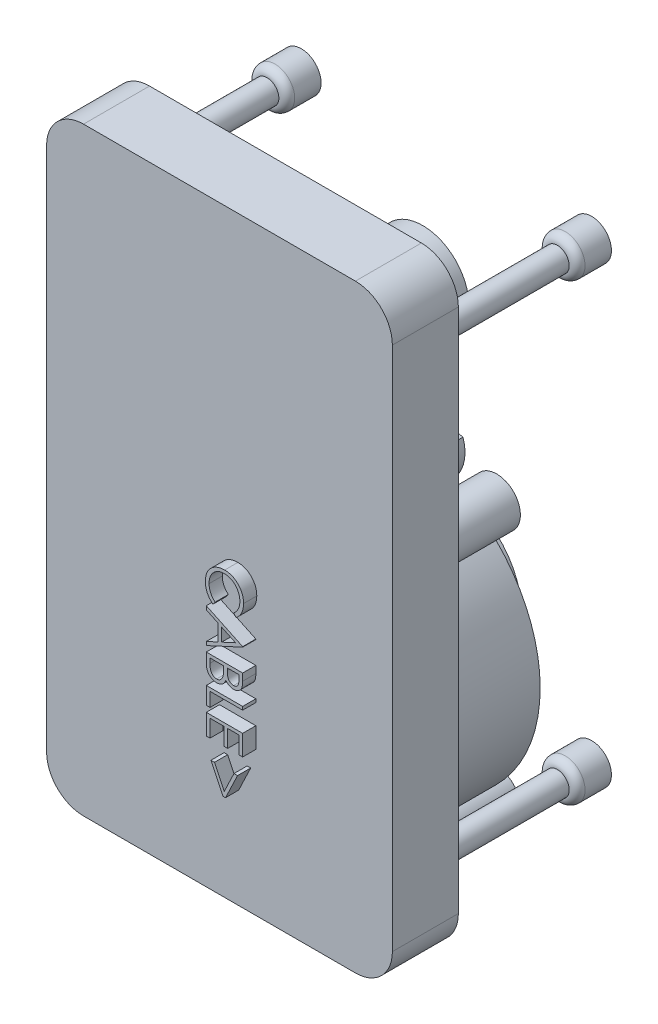
SolidWorks part; units mm, degrees
ref_plane "Front Plane" through (0, 0, 0) normal (0, 0, 1) x (1, 0, 0)
ref_plane "Top Plane" through (0, 0, 0) normal (0, 1, 0) x (1, 0, 0)
ref_plane "Right Plane" through (0, 0, 0) normal (1, 0, 0) x (0, 0, -1)
sketch "Sketch1" plane through (0, 0, 0) normal (0, 0, 1) x (1, 0, 0)
  line L0 (-13.081, 28.829) -> (13.081, 28.829)
  line L1 (-16.637, 25.273) -> (-16.637, -25.273)
  line L2 (-13.081, -28.829) -> (13.081, -28.829)
  line L3 (16.637, 25.273) -> (16.637, -25.273)
  line L4 (-16.637, 28.829) -> (16.637, -28.829) construction
  line L5 (-16.637, -28.829) -> (16.637, 28.829) construction
  line L6 (0, 36.9388) -> (0, -36.9388) construction
  line L7 (-21.0275, 0) -> (21.0275, 0) construction
  arc A0 (16.637, -25.273) -> (13.081, -28.829) centre (13.081, -25.273) cw
  arc A1 (-13.081, -28.829) -> (-16.637, -25.273) centre (-13.081, -25.273) cw
  arc A2 (16.637, 25.273) -> (13.081, 28.829) centre (13.081, 25.273) ccw
  arc A3 (-13.081, 28.829) -> (-16.637, 25.273) centre (-13.081, 25.273) ccw
  circle A4 centre (0, -12.7) radius 7.239
  circle A5 centre (0, 12.7) radius 4.445
  circle A6 centre (0, 14.605) radius 6.35
  circle A7 centre (0, -12.7) radius 14.351
  arc A8 (-3.6204, 1.1868) -> (3.6204, 1.1868) centre (0, 0) ccw
  circle A9 centre (13.97, 21.844) radius 1.016
  circle A10 centre (-13.97, 21.844) radius 1.016
  circle A11 centre (13.97, -21.844) radius 1.016
  circle A12 centre (-13.97, -21.844) radius 1.016
  arc A13 (6.6635, 0.0102) -> (10.0641, -2.4694) centre (8.89, -0.508) cw
  arc A14 (-10.0641, -2.4694) -> (-6.6635, 0.0102) centre (-8.89, -0.508) cw
  arc A15 (-10.0641, -22.9306) -> (-6.6635, -25.4102) centre (-8.89, -24.892) ccw
  arc A16 (6.6635, -25.4102) -> (10.0641, -22.9306) centre (8.89, -24.892) ccw
  point P0 (0, 0)
  dimension "D3" = 3.556
  dimension "D4" = 14.478
  dimension "D5" = 8.89
  dimension "D6" = 12.7
  dimension "D8" = 7.62
  dimension "D10" = 2.032
  dimension "D12" = 28.702
  dimension "D13" = 2.286
  dimension "D1" = 33.274
  dimension "D2" = 57.658
  dimension "D7" = 12.7
  dimension "D9" = 21.844
  dimension "D11" = 13.97
  dimension "D14" = 8.89
  dimension "D15" = 0.508
  dimension "D16" = 0.508
  dimension "D17" = 8.89
  dimension "D18" = 24.892
  dimension "D19" = 24.892
  dimension "D20" = 8.89
  dimension "D21" = 8.89
extrude "Boss-Extrude1" add sketch "Sketch1" against normal blind 10.16 contours A8 A7 A4 | A14 A7 | A7 A8 | A13 A7 | A7 A16 | A7 A15 | A4 region at (0, -12.7, 0) region at (12.8646, -18.0906, 0) region at (9.2197, -0.0559, 0) region at (9.2197, -25.3441, 0) region at (0, -0.8411, 0) region at (-9.2197, -25.3441, 0) region at (-9.2197, -0.0559, 0)
sketch "Sketch2" plane through (0, 0, 0) normal (0, 0, 1) x (1, 0, 0)
  line L0 (-13.081, 28.829) -> (13.081, 28.829)
  line L1 (-16.637, 25.273) -> (-16.637, -25.273)
  line L2 (-13.081, -28.829) -> (13.081, -28.829)
  line L3 (16.637, 25.273) -> (16.637, -25.273)
  line L4 (-16.637, 28.829) -> (16.637, -28.829) construction
  line L5 (-16.637, -28.829) -> (16.637, 28.829) construction
  line L6 (0, 38.9705) -> (0, -34.9071) construction
  line L7 (-9.8575, 0) -> (32.1974, 0) construction
  arc A0 (16.637, -25.273) -> (13.081, -28.829) centre (13.081, -25.273) cw
  arc A1 (-13.081, -28.829) -> (-16.637, -25.273) centre (-13.081, -25.273) cw
  arc A2 (16.637, 25.273) -> (13.081, 28.829) centre (13.081, 25.273) ccw
  arc A3 (-13.081, 28.829) -> (-16.637, 25.273) centre (-13.081, 25.273) ccw
  circle A4 centre (0, -12.7) radius 7.239
  circle A5 centre (0, 12.7) radius 4.445
  circle A6 centre (0, 14.605) radius 6.35
  circle A7 centre (0, -12.7) radius 14.351
  arc A8 (-3.6204, 1.1868) -> (3.6204, 1.1868) centre (0, 0) ccw
  circle A9 centre (13.97, 21.844) radius 1.016
  circle A10 centre (-13.97, 21.844) radius 1.016
  circle A11 centre (13.97, -21.844) radius 1.016
  circle A12 centre (-13.97, -21.844) radius 1.016
  arc A13 (6.6635, 0.0102) -> (10.0641, -2.4694) centre (8.89, -0.508) cw
  arc A14 (-10.0641, -2.4694) -> (-6.6635, 0.0102) centre (-8.89, -0.508) cw
  arc A15 (-10.0641, -22.9306) -> (-6.6635, -25.4102) centre (-8.89, -24.892) ccw
  arc A16 (6.6635, -25.4102) -> (10.0641, -22.9306) centre (8.89, -24.892) ccw
  point P0 (0, 0)
  dimension "D3" = 3.556
  dimension "D4" = 14.478
  dimension "D5" = 8.89
  dimension "D6" = 12.7
  dimension "D8" = 7.62
  dimension "D10" = 2.032
  dimension "D12" = 28.702
  dimension "D13" = 2.286
  dimension "D1" = 33.274
  dimension "D2" = 57.658
  dimension "D7" = 12.7
  dimension "D9" = 21.844
  dimension "D11" = 13.97
  dimension "D14" = 8.89
  dimension "D15" = 0.508
  dimension "D16" = 0.508
  dimension "D17" = 8.89
  dimension "D18" = 24.892
  dimension "D19" = 24.892
  dimension "D20" = 8.89
  dimension "D21" = 8.89
extrude "Boss-Extrude2" add sketch "Sketch2" against normal blind 1.778 separate body contours A5 | A5 A6 region at (0, 12.7, 0) region at (-4.3631, 18.9681, 0)
sketch "Sketch3" plane through (0, 0, -10.16) normal (0, 0, -1) x (-1, 0, 0)
  circle A0 centre (-8.89, -0.508) radius 2.286
  circle A1 centre (8.89, -24.892) radius 2.286
  circle A2 centre (-8.89, -24.892) radius 2.286
  circle A3 centre (8.89, -0.508) radius 2.286
extrude "Boss-Extrude3" add sketch "Sketch3" along normal blind 1.27
sketch "Sketch4" plane through (0, 0, -10.16) normal (0, 0, -1) x (-1, 0, 0)
  line L0 (-13.081, 28.829) -> (13.081, 28.829)
  line L1 (-16.637, 25.273) -> (-16.637, -25.273)
  line L2 (-13.081, -28.829) -> (13.081, -28.829)
  line L3 (16.637, 25.273) -> (16.637, -25.273)
  line L4 (-16.637, 28.829) -> (16.637, -28.829) construction
  line L5 (-16.637, -28.829) -> (16.637, 28.829) construction
  line L6 (0, 23.9866) -> (0, -49.891) construction
  line L7 (7.1619, 0) -> (49.2169, 0) construction
  arc A0 (16.637, -25.273) -> (13.081, -28.829) centre (13.081, -25.273) cw
  arc A1 (-13.081, -28.829) -> (-16.637, -25.273) centre (-13.081, -25.273) cw
  arc A2 (16.637, 25.273) -> (13.081, 28.829) centre (13.081, 25.273) ccw
  arc A3 (-13.081, 28.829) -> (-16.637, 25.273) centre (-13.081, 25.273) ccw
  circle A4 centre (0, -12.7) radius 7.239
  circle A5 centre (0, 12.7) radius 4.445
  circle A6 centre (0, 14.605) radius 6.35
  circle A7 centre (0, -12.7) radius 14.351
  arc A8 (-3.6204, 1.1868) -> (3.6204, 1.1868) centre (0, 0) ccw
  circle A9 centre (13.97, 21.844) radius 1.016
  circle A10 centre (-13.97, 21.844) radius 1.016
  circle A11 centre (13.97, -21.844) radius 1.016
  circle A12 centre (-13.97, -21.844) radius 1.016
  arc A13 (6.6635, 0.0102) -> (10.0641, -2.4694) centre (8.89, -0.508) cw
  arc A14 (-10.0641, -2.4694) -> (-6.6635, 0.0102) centre (-8.89, -0.508) cw
  arc A15 (-10.0641, -22.9306) -> (-6.6635, -25.4102) centre (-8.89, -24.892) ccw
  arc A16 (6.6635, -25.4102) -> (10.0641, -22.9306) centre (8.89, -24.892) ccw
  point P0 (0, 0)
  dimension "D3" = 3.556
  dimension "D4" = 14.478
  dimension "D5" = 8.89
  dimension "D6" = 12.7
  dimension "D8" = 7.62
  dimension "D10" = 2.032
  dimension "D12" = 28.702
  dimension "D13" = 2.286
  dimension "D1" = 33.274
  dimension "D2" = 57.658
  dimension "D7" = 12.7
  dimension "D9" = 21.844
  dimension "D11" = 13.97
  dimension "D14" = 8.89
  dimension "D15" = 0.508
  dimension "D16" = 0.508
  dimension "D17" = 8.89
  dimension "D18" = 24.892
  dimension "D19" = 24.892
  dimension "D20" = 8.89
  dimension "D21" = 8.89
extrude "Boss-Extrude4" add sketch "Sketch4" along normal blind 3.302 contours A7 A8 region at (0, -0.8411, -10.16)
sketch "Sketch5" plane through (0, 0, -1.778) normal (0, 0, -1) x (-1, 0, 0)
  line L0 (-13.081, 28.829) -> (13.081, 28.829)
  line L1 (-16.637, 25.273) -> (-16.637, -25.273)
  line L2 (-13.081, -28.829) -> (13.081, -28.829)
  line L3 (16.637, 25.273) -> (16.637, -25.273)
  line L4 (-16.637, 28.829) -> (16.637, -28.829) construction
  line L5 (-16.637, -28.829) -> (16.637, 28.829) construction
  line L6 (0, 36.0331) -> (0, -37.8445) construction
  line L7 (26.8703, 0) -> (68.9252, 0) construction
  arc A0 (16.637, -25.273) -> (13.081, -28.829) centre (13.081, -25.273) cw
  arc A1 (-13.081, -28.829) -> (-16.637, -25.273) centre (-13.081, -25.273) cw
  arc A2 (16.637, 25.273) -> (13.081, 28.829) centre (13.081, 25.273) ccw
  arc A3 (-13.081, 28.829) -> (-16.637, 25.273) centre (-13.081, 25.273) ccw
  circle A4 centre (0, -12.7) radius 7.239
  circle A5 centre (0, 12.7) radius 4.445
  circle A6 centre (0, 14.605) radius 6.35
  circle A7 centre (0, -12.7) radius 14.351
  arc A8 (-3.6204, 1.1868) -> (3.6204, 1.1868) centre (0, 0) ccw
  circle A9 centre (13.97, 21.844) radius 1.016
  circle A10 centre (-13.97, 21.844) radius 1.016
  circle A11 centre (13.97, -21.844) radius 1.016
  circle A12 centre (-13.97, -21.844) radius 1.016
  arc A13 (6.6635, 0.0102) -> (10.0641, -2.4694) centre (8.89, -0.508) cw
  arc A14 (-10.0641, -2.4694) -> (-6.6635, 0.0102) centre (-8.89, -0.508) cw
  arc A15 (-10.0641, -22.9306) -> (-6.6635, -25.4102) centre (-8.89, -24.892) ccw
  arc A16 (6.6635, -25.4102) -> (10.0641, -22.9306) centre (8.89, -24.892) ccw
  point P0 (0, 0)
  dimension "D3" = 3.556
  dimension "D4" = 14.478
  dimension "D5" = 8.89
  dimension "D6" = 12.7
  dimension "D8" = 7.62
  dimension "D10" = 2.032
  dimension "D12" = 28.702
  dimension "D13" = 2.286
  dimension "D1" = 33.274
  dimension "D2" = 57.658
  dimension "D7" = 12.7
  dimension "D9" = 21.844
  dimension "D11" = 13.97
  dimension "D14" = 8.89
  dimension "D15" = 0.508
  dimension "D16" = 0.508
  dimension "D17" = 8.89
  dimension "D18" = 24.892
  dimension "D19" = 24.892
  dimension "D20" = 8.89
  dimension "D21" = 8.89
extrude "Boss-Extrude5" add sketch "Sketch5" along normal blind 11.43 contours A5 region at (0, 12.7, -1.778)
sketch "Sketch6" plane through (0, 0, 0) normal (0, 0, 1) x (1, 0, 0)
  line L0 (-13.081, 28.829) -> (13.081, 28.829)
  line L1 (-16.637, 25.273) -> (-16.637, -25.273)
  line L2 (-13.081, -28.829) -> (13.081, -28.829)
  line L3 (16.637, 25.273) -> (16.637, -25.273)
  line L4 (-16.637, 28.829) -> (16.637, -28.829) construction
  line L5 (-16.637, -28.829) -> (16.637, 28.829) construction
  line L6 (0, 36.0885) -> (0, -37.789) construction
  line L7 (-47.9194, 0) -> (-5.8644, 0) construction
  arc A0 (16.637, -25.273) -> (13.081, -28.829) centre (13.081, -25.273) cw
  arc A1 (-13.081, -28.829) -> (-16.637, -25.273) centre (-13.081, -25.273) cw
  arc A2 (16.637, 25.273) -> (13.081, 28.829) centre (13.081, 25.273) ccw
  arc A3 (-13.081, 28.829) -> (-16.637, 25.273) centre (-13.081, 25.273) ccw
  circle A4 centre (0, -12.7) radius 7.239
  circle A5 centre (0, 12.7) radius 4.445
  circle A6 centre (0, 14.605) radius 6.35
  circle A7 centre (0, -12.7) radius 14.351
  arc A8 (-3.6204, 1.1868) -> (3.6204, 1.1868) centre (0, 0) ccw
  circle A9 centre (13.97, 21.844) radius 1.143
  circle A10 centre (-13.97, 21.844) radius 1.143
  circle A11 centre (13.97, -21.844) radius 1.143
  circle A12 centre (-13.97, -21.844) radius 1.143
  arc A13 (6.6635, 0.0102) -> (10.0641, -2.4694) centre (8.89, -0.508) cw
  arc A14 (-10.0641, -2.4694) -> (-6.6635, 0.0102) centre (-8.89, -0.508) cw
  arc A15 (-10.0641, -22.9306) -> (-6.6635, -25.4102) centre (-8.89, -24.892) ccw
  arc A16 (6.6635, -25.4102) -> (10.0641, -22.9306) centre (8.89, -24.892) ccw
  point P0 (0, 0)
  dimension "D3" = 3.556
  dimension "D4" = 14.478
  dimension "D5" = 8.89
  dimension "D6" = 12.7
  dimension "D8" = 7.62
  dimension "D10" = 2.286
  dimension "D12" = 28.702
  dimension "D13" = 2.286
  dimension "D1" = 33.274
  dimension "D2" = 57.658
  dimension "D7" = 12.7
  dimension "D9" = 21.844
  dimension "D11" = 13.97
  dimension "D14" = 8.89
  dimension "D15" = 0.508
  dimension "D16" = 0.508
  dimension "D17" = 8.89
  dimension "D18" = 24.892
  dimension "D19" = 24.892
  dimension "D20" = 8.89
  dimension "D21" = 8.89
extrude "Boss-Extrude6" add sketch "Sketch6" against normal blind 15.494 separate body contours A10 | A9 | A12 | A11 region at (13.97, 21.844, 0) region at (-13.97, 21.844, 0) region at (13.97, -21.844, 0) region at (-13.97, -21.844, 0)
sketch "Sketch7" plane through (0, 0, -10.16) normal (0, 0, -1) x (-1, 0, 0)
  line L0 (-13.081, 28.829) -> (13.081, 28.829)
  line L1 (-16.637, 25.273) -> (-16.637, -25.273)
  line L2 (-13.081, -28.829) -> (13.081, -28.829)
  line L3 (16.637, 25.273) -> (16.637, -25.273)
  line L4 (-16.637, 28.829) -> (16.637, -28.829) construction
  line L5 (-16.637, -28.829) -> (16.637, 28.829) construction
  line L6 (0, 26.9541) -> (0, -46.9235) construction
  line L7 (8.0915, 0) -> (50.1464, 0) construction
  arc A0 (16.637, -25.273) -> (13.081, -28.829) centre (13.081, -25.273) cw
  arc A1 (-13.081, -28.829) -> (-16.637, -25.273) centre (-13.081, -25.273) cw
  arc A2 (16.637, 25.273) -> (13.081, 28.829) centre (13.081, 25.273) ccw
  arc A3 (-13.081, 28.829) -> (-16.637, 25.273) centre (-13.081, 25.273) ccw
  circle A4 centre (0, -12.7) radius 7.239
  circle A5 centre (0, 12.7) radius 4.445
  circle A6 centre (0, 14.605) radius 6.35
  circle A7 centre (0, -12.7) radius 14.351
  arc A8 (-3.6204, 1.1868) -> (3.6204, 1.1868) centre (0, 0) ccw
  circle A9 centre (13.97, 21.844) radius 1.016
  circle A10 centre (-13.97, 21.844) radius 1.016
  circle A11 centre (13.97, -21.844) radius 1.016
  circle A12 centre (-13.97, -21.844) radius 1.016
  arc A13 (6.6635, 0.0102) -> (10.0641, -2.4694) centre (8.89, -0.508) cw
  arc A14 (-10.0641, -2.4694) -> (-6.6635, 0.0102) centre (-8.89, -0.508) cw
  arc A15 (-10.0641, -22.9306) -> (-6.6635, -25.4102) centre (-8.89, -24.892) ccw
  arc A16 (6.6635, -25.4102) -> (10.0641, -22.9306) centre (8.89, -24.892) ccw
  point P0 (0, 0)
  dimension "D3" = 3.556
  dimension "D4" = 14.478
  dimension "D5" = 8.89
  dimension "D6" = 12.7
  dimension "D8" = 7.62
  dimension "D10" = 2.032
  dimension "D12" = 28.702
  dimension "D13" = 2.286
  dimension "D1" = 33.274
  dimension "D2" = 57.658
  dimension "D7" = 12.7
  dimension "D9" = 21.844
  dimension "D11" = 13.97
  dimension "D14" = 8.89
  dimension "D15" = 0.508
  dimension "D16" = 0.508
  dimension "D17" = 8.89
  dimension "D18" = 24.892
  dimension "D19" = 24.892
  dimension "D20" = 8.89
  dimension "D21" = 8.89
extrude "Boss-Extrude7" add sketch "Sketch7" along normal blind 5.334 contours A4 region at (0, -12.7, -10.16)
sketch "Sketch8" plane through (0, 0, 0) normal (0, 0, 1) x (1, 0, 0)
  line L1 (-13.081, 28.829) -> (13.081, 28.829)
  line L2 (-16.637, 25.273) -> (-16.637, -25.273)
  line L3 (-13.081, -28.829) -> (13.081, -28.829)
  line L4 (16.637, 25.273) -> (16.637, -25.273)
  line L5 (-16.637, 28.829) -> (16.637, -28.829) construction
  line L6 (-16.637, -28.829) -> (16.637, 28.829) construction
  arc A8 (16.637, -25.273) -> (13.081, -28.829) centre (13.081, -25.273) cw
  arc A13 (-13.081, -28.829) -> (-16.637, -25.273) centre (-13.081, -25.273) cw
  arc A14 (16.637, 25.273) -> (13.081, 28.829) centre (13.081, 25.273) ccw
  arc A15 (-13.081, 28.829) -> (-16.637, 25.273) centre (-13.081, 25.273) ccw
  point P0 (0, 0)
  dimension "D3" = 3.556
  dimension "D1" = 33.274
  dimension "D23" = 57.658
extrude "Boss-Extrude8" add sketch "Sketch8" along normal blind 6.35
sketch "Sketch9" plane through (0, 0, -15.494) normal (0, 0, -1) x (-1, 0, 0)
  circle A0 centre (-13.97, 21.844) radius 1.905
  circle A1 centre (13.97, 21.844) radius 1.905
  circle A2 centre (13.97, -21.844) radius 1.905
  circle A3 centre (-13.97, -21.844) radius 1.905
  dimension "D1" = 3.81
extrude "Boss-Extrude9" add sketch "Sketch9" against normal blind 3.302
sketch "Sketch10" plane through (0, 0, 6.35) normal (0, 0, 1) x (1, 0, 0)
  line L0 (0, 0) -> (0, -28.829) construction
  line L1 (-13.081, -28.829) -> (13.081, -28.829) construction
  text T0 "CABLE >"
extrude "Boss-Extrude10" add sketch "Sketch10" along normal blind 1.27
fillet "Fillet1" radius 0.762 4 edges at (-15.875, 21.844, -12.192) (12.065, 21.844, -12.192) (-15.875, -21.844, -12.192) (12.065, -21.844, -12.192)
